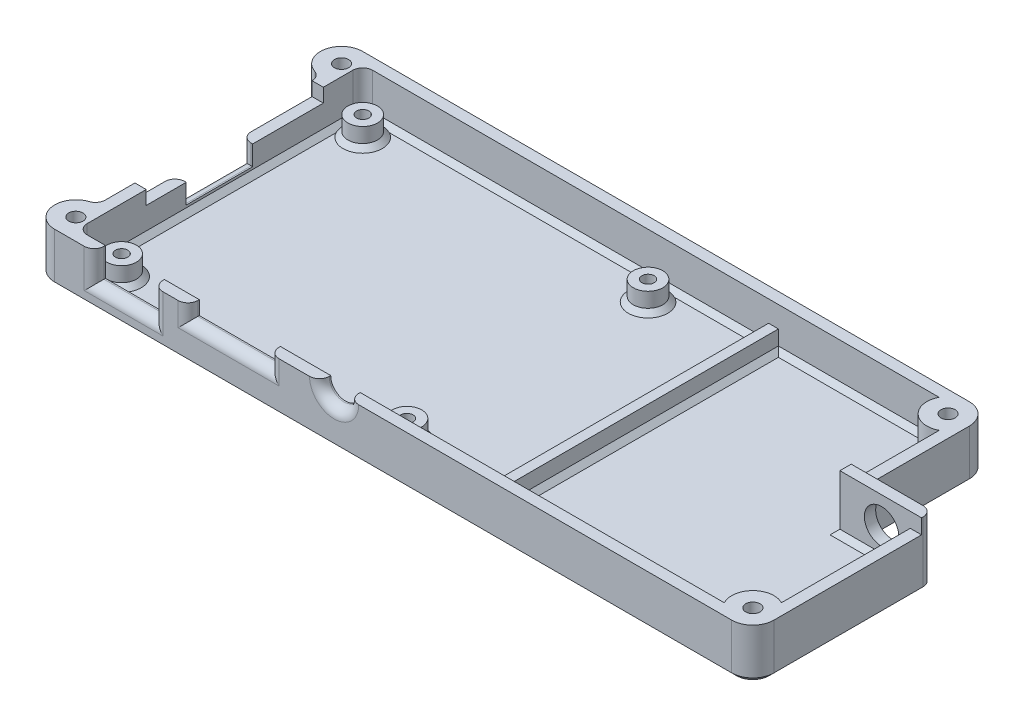
SolidWorks part; units mm, degrees
ref_plane "Front Plane" through (0, 0, 0) normal (0, 0, 1) x (1, 0, 0)
ref_plane "Top Plane" through (0, 0, 0) normal (0, 1, 0) x (1, 0, 0)
ref_plane "Right Plane" through (0, 0, 0) normal (1, 0, 0) x (0, 0, -1)
sketch "Sketch1" plane through (0, 0, 0) normal (0, 1, 0) x (1, 0, 0)
  line L0 (-71.5618, 3.106) -> (49.4382, 3.106) construction
  line L1 (-71.5618, 31.106) -> (49.4382, 31.106)
  line L2 (-71.5618, 31.106) -> (-71.5618, -24.894)
  line L3 (-71.5618, -24.894) -> (49.4382, -24.894)
  line L4 (49.4382, 31.106) -> (49.4382, -24.894)
  line L5 (-60.6618, -24.894) -> (-60.6618, -31.6828) construction
  line L6 (-68.0618, 27.606) -> (-10.0618, 27.606)
  line L7 (-68.0618, 27.606) -> (-68.0618, -21.394)
  line L8 (-68.0618, -21.394) -> (-10.0618, -21.394)
  line L9 (-10.0618, 27.606) -> (-10.0618, -21.394)
  line L10 (-39.5618, -24.894) -> (-39.5618, -31.6828) construction
  line L11 (-18.0618, -24.894) -> (-18.0618, -31.6828) construction
  line L12 (-65.4118, -26.5648) -> (-55.9118, -26.5648) construction
  line L13 (-48.0618, -26.5648) -> (-31.0618, -26.5648) construction
  line L14 (-22.0618, -26.5648) -> (-14.0618, -26.5648) construction
  line L15 (-72.5618, 9.606) -> (-72.5618, -3.394) construction
  line L16 (-71.5618, 3.106) -> (-72.5618, 3.106) construction
  dimension "D1" = 121
  dimension "D2" = 56
  dimension "D3" = 49
  dimension "D4" = 58
  dimension "D5" = 3.5
  dimension "D6" = 3.5
  dimension "D7" = 10.9
  dimension "D8" = 32
  dimension "D9" = 53.5
  dimension "D10" = 2
  dimension "D11" = 13
  dimension "D12" = 9.5
  dimension "D13" = 17
  dimension "D14" = 8
sketch "Sketch3" plane through (0, 0, 0) normal (0, 1, 0) x (1, 0, 0)
  line L0 (55.0382, -25.894) -> (64.7382, -25.894)
  line L1 (52.7382, 8.406) -> (67.0382, 8.406)
  line L2 (55.0382, 6.106) -> (64.7382, 6.106) construction
  line L3 (52.7382, -28.194) -> (67.0382, -28.194)
  line L4 (52.7382, 34.406) -> (-74.8618, 34.406)
  line L5 (-74.8618, 34.406) -> (-74.8618, -28.194)
  line L6 (-74.8618, -28.194) -> (52.7382, -28.194)
  line L7 (52.7382, 8.406) -> (52.7382, 34.406)
  line L8 (50.4382, 32.106) -> (-72.5618, 32.106)
  line L9 (50.4382, -25.894) -> (50.4382, 32.106)
  line L10 (-72.5618, -25.894) -> (50.4382, -25.894)
  line L11 (-72.5618, 32.106) -> (-72.5618, -25.894)
  line L12 (50.4382, 32.106) -> (-72.5618, 32.106)
  line L13 (50.4382, 6.106) -> (50.4382, 32.106)
  line L14 (-72.5618, -25.894) -> (50.4382, -25.894)
  line L15 (-72.5618, 32.106) -> (-72.5618, -25.894)
  line L16 (-11.0618, 3.106) -> (-11.0618, 34.406) construction
  line L17 (-71.5618, 3.106) -> (49.4382, 3.106) construction
  line L18 (67.0382, 8.406) -> (67.0382, -28.194)
  line L19 (64.7382, 6.106) -> (64.7382, -25.894)
  line L20 (-74.8618, 3.106) -> (52.7382, 3.106) construction
  line L21 (50.4382, 6.106) -> (64.7382, 6.106)
  line L22 (55.0382, -25.894) -> (50.4382, -25.894)
  line L23 (55.0382, 6.106) -> (55.0382, -25.894) construction
  line L24 (52.7382, 8.406) -> (52.7382, -28.194) construction
  line L25 (52.7382, -28.194) -> (52.7382, 34.406) construction
  line L26 (50.4382, -25.894) -> (50.4382, 32.106) construction
  dimension "D3" = 2.3
  dimension "D4" = 26
  dimension "D5" = 12
  dimension "D1" = 1
  dimension "D2" = 2.3
extrude "Boss-Extrude1" add sketch "Sketch3" along normal blind 10.3
sketch "Sketch5" plane through (0, 0, 0) normal (0, 1, 0) x (1, 0, 0)
  line L1 (-72.5618, 32.106) -> (50.4382, 32.106)
  line L2 (-72.5618, 32.106) -> (-72.5618, -25.894)
  line L3 (-72.5618, -25.894) -> (50.4382, -25.894)
  line L4 (50.4382, 32.106) -> (50.4382, 6.106)
  line L5 (50.4382, 6.106) -> (64.7382, 6.106)
  line L7 (50.4382, -25.894) -> (64.7382, -25.894)
  line L8 (64.7382, 6.106) -> (64.7382, -25.894)
extrude "Boss-Extrude2" add sketch "Sketch5" along normal blind 2
sketch "Sketch6" plane through (0, 2, 0) normal (0, 1, 0) x (1, 0, 0)
  circle A0 centre (-68.0618, 27.606) radius 3
  circle A1 centre (-68.0618, -21.394) radius 3
  circle A2 centre (-10.0618, -21.394) radius 3
  circle A3 centre (-10.0618, 27.606) radius 3
extrude "Boss-Extrude3" add sketch "Sketch6" along normal blind 4
hole_wizard "Ø2.5 (2.5) Diameter Hole1" positions "Sketch8" profile "Sketch9" hole size "Ø2.5" standard "ANSI Metric"
sketch "Sketch8" plane through (0, 6, 0) normal (0, 1, 0) x (1, 0, 0)
  point P0 (-68.0618, 27.606)
  point P3 (-10.0618, 27.606)
  point P6 (-10.0618, -21.394)
  point P9 (-68.0618, -21.394)
sketch "Sketch9" plane through (-68.0618, 6, -27.606) normal (1, 0, 0) x (0, 0, 1)
  line L0 (0, 0) -> (0, 8.7511)
  line L1 (0, 8.7511) -> (1.25, 8)
  line L2 (1.25, 8) -> (1.25, 0)
  line L5 (1.25, 0) -> (0, 0)
  line L10 (0, 8.7511) -> (-1.25, 8) construction
  line L11 (0, -6.35) -> (0, 107.95) construction
  dimension "Hole Dia." = 2.5
  dimension "Hole Depth" = 8
  dimension "Drill Angle" = 118
sketch "Sketch10" plane through (0, 2, 0) normal (0, 1, 0) x (1, 0, 0)
  line L0 (50.4382, 32.106) -> (-72.5618, 32.106) construction
  line L1 (9.9382, 32.106) -> (11.9382, 32.106)
  line L2 (9.9382, 32.106) -> (9.9382, -25.894)
  line L3 (9.9382, -25.894) -> (11.9382, -25.894)
  line L4 (11.9382, 32.106) -> (11.9382, -25.894)
  line L5 (-72.5618, -25.894) -> (64.7382, -25.894) construction
  line L6 (-10.0618, 27.606) -> (-10.0618, -21.394) construction
  dimension "D1" = 2
  dimension "D2" = 20
extrude "Boss-Extrude4" add sketch "Sketch10" along normal blind 4
sketch "Sketch11" plane through (0, 0, 28.194) normal (0, 0, 1) x (1, 0, 0)
  line L0 (-74.8618, 10.3) -> (-74.8618, 0) construction
  line L1 (-66.8618, 10.3) -> (-54.8618, 10.3)
  line L2 (-66.8618, 10.3) -> (-66.8618, 4.5)
  line L3 (-66.8618, 4.5) -> (-54.8618, 4.5)
  line L4 (-54.8618, 10.3) -> (-54.8618, 4.5)
  line L5 (-74.8618, 0) -> (67.0382, 0) construction
  line L6 (-60.8618, 10.3) -> (-60.6618, 0) construction
  line L7 (-65.4118, 0) -> (-55.9118, 0) construction
  line L9 (-47.778, 10.3) -> (-31.278, 10.3)
  line L10 (-47.778, 10.3) -> (-47.778, 7.5)
  line L11 (-47.778, 7.5) -> (-31.278, 7.5)
  line L12 (-31.278, 10.3) -> (-31.278, 7.5)
  line L13 (-68.0618, 0) -> (-10.0618, 0) construction
  line L14 (-39.5618, 0) -> (-39.528, 10.3) construction
  line L15 (-48.0618, 0) -> (-31.0618, 0) construction
  line L16 (-18.0618, 0) -> (-18.0618, 10.3) construction
  line L17 (-22.0618, 0) -> (-14.0618, 0) construction
  line L18 (-74.8618, 10.3) -> (67.0382, 10.3) construction
  circle A0 centre (-18.0618, 10.3) radius 3
  dimension "D5" = 6
  dimension "D1" = 4.5
  dimension "D2" = 12
  dimension "D3" = 7.5
  dimension "D4" = 16.5
  dimension "D6" = 8
extrude "Cut-Extrude1" cut sketch "Sketch11" against normal up to next
sketch "Sketch12" plane through (-74.8618, 0, 0) normal (-1, 0, 0) x (0, 0, 1)
  line L0 (-3.106, 0) -> (-3.106, 10.3) construction
  line L1 (-27.606, 0) -> (21.394, 0) construction
  line L2 (-34.406, 10.3) -> (28.194, 10.3) construction
  line L4 (-9.7329, 10.3) -> (3.7671, 10.3)
  line L5 (-9.7329, 10.3) -> (-9.7329, 3.5)
  line L6 (-9.7329, 3.5) -> (3.7671, 3.5)
  line L7 (3.7671, 10.3) -> (3.7671, 3.5)
  line L8 (-24.106, 10.3) -> (11.894, 10.3)
  line L9 (-24.106, 10.3) -> (-24.106, 7.5)
  line L10 (-24.106, 7.5) -> (11.894, 7.5)
  line L11 (11.894, 10.3) -> (11.894, 7.5)
  dimension "D1" = 13.5
  dimension "D2" = 3.5
  dimension "D3" = 7.5
  dimension "D4" = 36
extrude "Cut-Extrude2" cut sketch "Sketch12" against normal up to next contours L10 L11 L8 L9 | L7 L6 L5 L4
fillet "Fillet6" radius 2 1 edges at (50.4382, 6.15, -32.106)
fillet "Fillet8" radius 2 2 edges at (-72.5618, 6.15, 25.894) (-72.5618, 6.15, -32.106)
chamfer "Chamfer1" distance 1 angle 45 4 edges at (-68.0618, 2, 24.394) (-10.0618, 2, 24.394) (-10.0618, 2, -24.606) (-68.0618, 2, -24.606)
chamfer "Chamfer2" distance 1 angle 45 13 edges at (11.9382, 2, -3.106) (38.3382, 2, 25.894) (30.1882, 2, -32.106) (49.8524, 2, -31.5202) (50.4382, 2, -18.106) (-30.3118, 2, 25.894) (-71.976, 2, 25.3082) (-72.5618, 2, -3.106) (-71.976, 2, -31.5202) (9.9382, 2, -3.106) (-30.3118, 2, -32.106) (64.7382, 2, 9.894) (57.5882, 2, -6.106)
fillet "Fillet9" radius 2 9 edges at (-74.8618, 5.5, -9.7329) (-74.8618, 3.5, -2.9829) (-74.8618, 5.5, 3.7671) (-18.0618, 7.3, 28.194) (-31.278, 8.9, 28.194) (-47.778, 8.9, 28.194) (-39.528, 7.5, 28.194) (-54.8618, 7.4, 28.194) (-60.8618, 4.5, 28.194)
sketch "Sketch14" plane through (0, 10.3, 0) normal (0, 1, 0) x (1, 0, 0)
  line L1 (50.4382, 6.106) -> (67.0382, 6.106)
  line L2 (50.4382, 6.106) -> (50.4382, 8.406)
  line L3 (50.4382, 8.406) -> (67.0382, 8.406)
  line L4 (67.0382, 6.106) -> (67.0382, 8.406)
extrude "Boss-Extrude5" add sketch "Sketch14" along normal blind 3
sketch "Sketch13" plane through (0, 0, -8.406) normal (0, 0, -1) x (-1, 0, 0)
  circle A0 centre (-58.909, 7.7223) radius 3.5
extrude "Cut-Extrude3" cut sketch "Sketch13" against normal up to next
sketch "Sketch17" plane through (0, 0, 0) normal (0, 1, 0) x (1, 0, 0)
  line L0 (-74.8618, 34.406) -> (-74.8618, 24.106) construction
  line L1 (-74.8618, 34.406) -> (-74.8618, 25.806)
  line L2 (-74.8618, 25.806) -> (-74.659, 25.9406)
  line L3 (-74.8618, -19.594) -> (-74.8618, -28.194)
  line L4 (-74.8618, -28.194) -> (-74.659, -28.0594)
  arc A0 (-74.8618, -19.594) -> (-74.8618, -28.194) centre (-74.8618, -23.894) ccw
  arc A1 (-74.8618, 34.406) -> (-74.8618, 25.806) centre (-74.8618, 30.106) ccw
extrude "Boss-Extrude6" add sketch "Sketch17" along normal up to vertex (10.3 mm away) contours L1 A1 | L3 A0 region at (-76.6867, 0, -30.106) region at (-76.6867, 0, 23.894) up to point (-74.8618, 10.3, 28.194)
hole_wizard "Ø2.9 (2.9) Diameter Hole2" positions "Sketch19" profile "Sketch18" hole size "Ø2.9" standard "ANSI Metric" end condition up to next
sketch "Sketch19" plane through (0, 10.3, 0) normal (0, 1, 0) x (1, 0, 0)
  point P0 (-74.8618, 30.106)
sketch "Sketch18" plane through (-74.8618, 10.3, -30.106) normal (1, 0, 0) x (0, 0, 1)
  line L0 (0, 0) -> (0, 10.3)
  line L1 (0, 10.3) -> (1.45, 10.3)
  line L2 (1.45, 10.3) -> (1.45, 0)
  line L5 (1.45, 0) -> (0, 0)
  line L11 (0, -6.35) -> (0, 107.95) construction
  dimension "Thru Hole Dia." = 2.9
  dimension "Thru Hole Depth" = 10.3
hole_wizard "Ø2.9 (2.9) Diameter Hole1" positions "Sketch21" profile "Sketch20" hole size "Ø2.9" standard "ANSI Metric" end condition up to next
sketch "Sketch21" plane through (0, 10.3, 0) normal (0, 1, 0) x (1, 0, 0)
  point P0 (-74.8618, -23.894)
sketch "Sketch20" plane through (-74.8618, 10.3, 23.894) normal (1, 0, 0) x (0, 0, 1)
  line L0 (0, 0) -> (0, 10.3)
  line L1 (0, 10.3) -> (1.45, 10.3)
  line L2 (1.45, 10.3) -> (1.45, 0)
  line L5 (1.45, 0) -> (0, 0)
  line L11 (0, -6.35) -> (0, 107.95) construction
  dimension "Thru Hole Dia." = 2.9
  dimension "Thru Hole Depth" = 10.3
sketch "Sketch24" plane through (0, 2, 0) normal (0, 1, 0) x (1, 0, 0)
  circle A0 centre (62.7384, -23.8858) radius 4.3
  circle A1 centre (48.4185, 30.106) radius 4.3
extrude "Boss-Extrude7" add sketch "Sketch24" along normal up to surface (8.3 mm away) up to face at (-74.8618, 10.3, 25.344)
hole_wizard "Ø2.9 (2.9) Diameter Hole3" positions "Sketch26" profile "Sketch25" hole size "Ø2.9" standard "ANSI Metric" end condition up to next
sketch "Sketch26" plane through (0, 10.3, 0) normal (0, 1, 0) x (1, 0, 0)
  point P0 (62.7384, -23.8858)
sketch "Sketch25" plane through (62.7384, 10.3, 23.8858) normal (1, 0, 0) x (0, 0, 1)
  line L0 (0, 0) -> (0, 10.3)
  line L1 (0, 10.3) -> (1.45, 10.3)
  line L2 (1.45, 10.3) -> (1.45, 0)
  line L5 (1.45, 0) -> (0, 0)
  line L11 (0, -6.35) -> (0, 107.95) construction
  dimension "Thru Hole Dia." = 2.9
  dimension "Thru Hole Depth" = 10.3
hole_wizard "Ø2.9 (2.9) Diameter Hole4" positions "Sketch28" profile "Sketch27" hole size "Ø2.9" standard "ANSI Metric" end condition up to next
sketch "Sketch28" plane through (0, 10.3, 0) normal (0, 1, 0) x (1, 0, 0)
  point P0 (48.4185, 30.106)
sketch "Sketch27" plane through (48.4185, 10.3, -30.106) normal (1, 0, 0) x (0, 0, 1)
  line L0 (0, 0) -> (0, 10.3)
  line L1 (0, 10.3) -> (1.45, 10.3)
  line L2 (1.45, 10.3) -> (1.45, 0)
  line L5 (1.45, 0) -> (0, 0)
  line L11 (0, -6.35) -> (0, 107.95) construction
  dimension "Thru Hole Dia." = 2.9
  dimension "Thru Hole Depth" = 10.3
fillet "Fillet10" radius 4.3 1 edges at (52.7382, 5.15, -34.406)
fillet "Fillet16" radius 4.3 1 edges at (67.0382, 5.15, 28.194)
fillet "Fillet17" radius 2 2 edges at (52.7382, 5.15, -8.406) (67.0382, 6.65, -8.406)
fillet "Fillet18" radius 2 2 edges at (-74.8618, 5.15, 19.594) (-74.8618, 5.15, -25.806)
chamfer "Chamfer3" distance 1 angle 45 14 edges at (51.4788, 0, -33.1466) (-13.2118, 0, -34.406) (52.7382, 0, -20.256) (-79.1058, 0, -30.7975) (53.324, 0, -8.9918) (-75.2385, 0, -25.3002) (59.8882, 0, -8.406) (-74.8618, 0, -3.106) (66.4524, 0, -7.8202) (-75.2385, 0, 19.0883) (67.0382, 0, 8.744) (-79.1058, 0, 24.5855) (65.7788, 0, 26.9346) (-6.0618, 0, 28.194)
fillet "Fillet19" radius 2 1 edges at (-66.8618, 6.4, 28.194)
